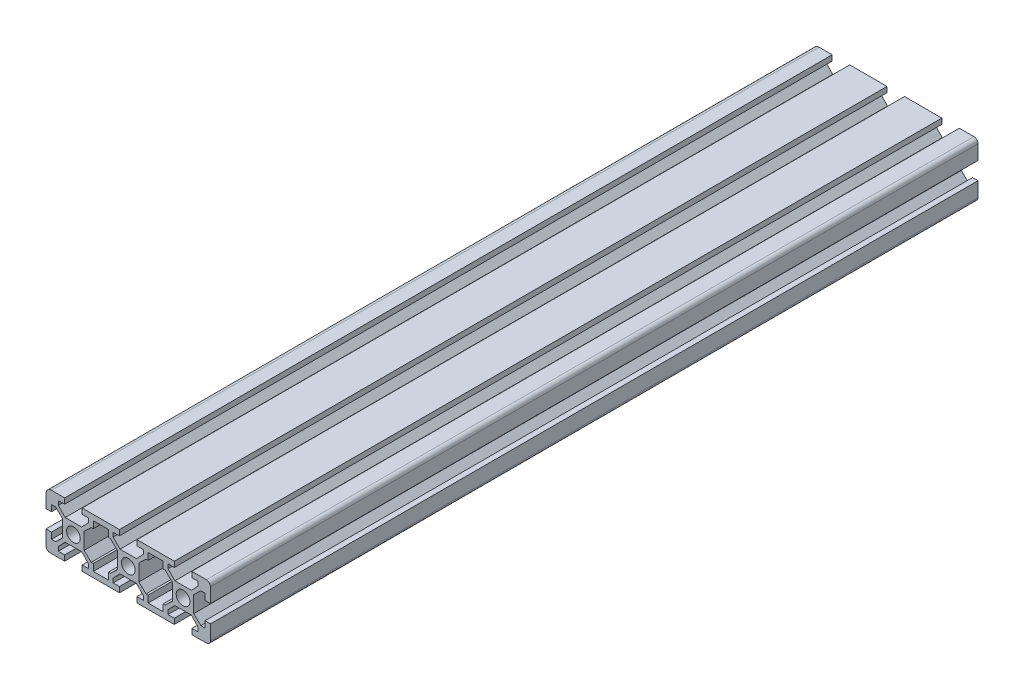
SolidWorks part; units mm, degrees
ref_plane "前视基准面" through (0, 0, 0) normal (0, 0, 1) x (1, 0, 0)
ref_plane "上视基准面" through (0, 0, 0) normal (0, 1, 0) x (1, 0, 0)
ref_plane "右视基准面" through (0, 0, 0) normal (1, 0, 0) x (0, 0, -1)
sketch "草图1" plane through (0, 0, 0) normal (0, 0, 1) x (1, 0, 0)
  line L1 (-28, 10) -> (28.5, 10)
  line L2 (-30, 8) -> (-30, -8.5)
  line L3 (-28.5, -10) -> (28.5, -10)
  line L4 (30, 8.5) -> (30, -8.5)
  line L5 (-30, 10) -> (30, -10) construction
  line L6 (-30, -10) -> (30, 10) construction
  line L7 (-30, -3.2) -> (-28, -3.2)
  line L13 (-16.8, 8) -> (-16.8, 10)
  line L14 (-14.5, 8) -> (-16.8, 8)
  line L15 (-14.5, 6.5) -> (-14.5, 8)
  line L16 (-17, 3.9) -> (-14.5, 6.5)
  line L17 (-23, 3.9) -> (-17, 3.9)
  line L18 (-25.5, 6.5) -> (-23, 3.9)
  line L25 (-28, -3.2) -> (-28, -5.5)
  line L26 (-28, -5.5) -> (-26.5, -5.5)
  line L27 (-26.5, -5.5) -> (-23.9, -3)
  line L28 (-23.9, -3) -> (-23.9, 3)
  line L29 (-23.9, 3) -> (-26.5, 5.5)
  line L30 (-26.5, 5.5) -> (-28, 5.5)
  line L31 (-28, 5.5) -> (-28, 3.2)
  line L32 (-28, 3.2) -> (-30, 3.2)
  line L33 (-25.5, 8) -> (-25.5, 6.5)
  line L34 (-23.2, 8) -> (-25.5, 8)
  line L35 (-23.2, 10) -> (-23.2, 8)
  line L36 (-12, -3.2) -> (-8, -3.2)
  line L37 (-12, -5.5) -> (-12, -3.2)
  line L38 (-13.5, -5.5) -> (-12, -5.5)
  line L39 (-16.1, -3) -> (-13.5, -5.5)
  line L40 (-16.1, 3) -> (-16.1, -3)
  line L41 (-13.5, 5.5) -> (-16.1, 3)
  line L42 (-12, 5.5) -> (-13.5, 5.5)
  line L43 (-12, 3.2) -> (-12, 5.5)
  line L44 (-8, 3.2) -> (-12, 3.2)
  line L45 (-23.2, -8) -> (-23.2, -10)
  line L46 (-25.5, -8) -> (-23.2, -8)
  line L47 (-25.5, -6.5) -> (-25.5, -8)
  line L48 (-23, -3.9) -> (-25.5, -6.5)
  line L49 (-17, -3.9) -> (-23, -3.9)
  line L50 (-14.5, -6.5) -> (-17, -3.9)
  line L51 (-14.5, -8) -> (-14.5, -6.5)
  line L52 (-16.8, -8) -> (-14.5, -8)
  line L53 (-16.8, -10) -> (-16.8, -8)
  line L54 (-10, 3.2) -> (-10, -3.2) construction
  line L55 (-10, -3.2) -> (-10, 3.2) construction
  line L56 (3, 3.9) -> (-3, 3.9)
  line L57 (5.5, 6.5) -> (3, 3.9)
  line L58 (5.5, 8) -> (5.5, 6.5)
  line L59 (3.2, 8) -> (5.5, 8)
  line L60 (3.2, 10) -> (3.2, 8)
  line L61 (-3.2, 8) -> (-3.2, 10)
  line L62 (-5.5, 8) -> (-3.2, 8)
  line L63 (-5.5, 6.5) -> (-5.5, 8)
  line L64 (-3, 3.9) -> (-5.5, 6.5)
  line L65 (-6.5, 5.5) -> (-3.9, 3)
  line L66 (-8, 5.5) -> (-6.5, 5.5)
  line L67 (-8, 3.2) -> (-8, 5.5)
  line L68 (-8, -5.5) -> (-8, -3.2)
  line L69 (-6.5, -5.5) -> (-8, -5.5)
  line L70 (-3.9, -3) -> (-6.5, -5.5)
  line L71 (-3.9, 3) -> (-3.9, -3)
  line L72 (-3, -3.9) -> (3, -3.9)
  line L73 (-5.5, -6.5) -> (-3, -3.9)
  line L74 (-5.5, -8) -> (-5.5, -6.5)
  line L75 (-3.2, -8) -> (-5.5, -8)
  line L76 (-3.2, -10) -> (-3.2, -8)
  line L77 (3.2, -8) -> (3.2, -10)
  line L78 (5.5, -8) -> (3.2, -8)
  line L79 (5.5, -6.5) -> (5.5, -8)
  line L80 (3, -3.9) -> (5.5, -6.5)
  line L81 (3.9, -3) -> (3.9, 3)
  line L82 (6.5, -5.5) -> (3.9, -3)
  line L83 (8, -5.5) -> (6.5, -5.5)
  line L84 (8, -3.2) -> (8, -5.5)
  line L85 (12, -3.2) -> (8, -3.2)
  line L86 (8, 3.2) -> (12, 3.2)
  line L87 (8, 5.5) -> (8, 3.2)
  line L88 (6.5, 5.5) -> (8, 5.5)
  line L89 (3.9, 3) -> (6.5, 5.5)
  line L90 (10, 3.2) -> (10, -3.133) construction
  line L91 (23.2, 8) -> (23.2, 10)
  line L92 (25.5, 8) -> (23.2, 8)
  line L93 (25.5, 6.5) -> (25.5, 8)
  line L94 (23, 3.9) -> (25.5, 6.5)
  line L95 (17, 3.9) -> (23, 3.9)
  line L96 (16.8, 10) -> (16.8, 8)
  line L97 (16.8, 8) -> (14.5, 8)
  line L98 (14.5, 8) -> (14.5, 6.5)
  line L99 (14.5, 6.5) -> (17, 3.9)
  line L100 (16.1, 3) -> (13.5, 5.5)
  line L101 (13.5, 5.5) -> (12, 5.5)
  line L102 (12, 5.5) -> (12, 3.2)
  line L103 (12, -3.2) -> (12, -5.5)
  line L104 (12, -5.5) -> (13.5, -5.5)
  line L105 (16.1, -3) -> (16.1, 3)
  line L106 (13.5, -5.5) -> (16.1, -3)
  line L107 (17, -3.9) -> (14.5, -6.5)
  line L108 (14.5, -6.5) -> (14.5, -8)
  line L109 (14.5, -8) -> (16.8, -8)
  line L110 (16.8, -8) -> (16.8, -10)
  line L111 (23.2, -10) -> (23.2, -8)
  line L112 (23.2, -8) -> (25.5, -8)
  line L113 (25.5, -8) -> (25.5, -6.5)
  line L114 (25.5, -6.5) -> (23, -3.9)
  line L115 (23, -3.9) -> (17, -3.9)
  line L116 (28, 3.2) -> (30, 3.2)
  line L117 (30, -3.2) -> (28, -3.2)
  line L118 (28, -5.5) -> (28, -3.2)
  line L119 (26.5, -5.5) -> (28, -5.5)
  line L120 (23.9, -3) -> (26.5, -5.5)
  line L121 (23.9, 3) -> (23.9, -3)
  line L122 (26.5, 5.5) -> (23.9, 3)
  line L123 (28, 5.5) -> (26.5, 5.5)
  line L124 (28, 3.2) -> (28, 5.5)
  line L125 (-12.75, 5.5) -> (-12.75, 8)
  line L126 (-7.25, 5.5) -> (-7.25, 8)
  line L127 (-7.25, 8) -> (-12.75, 8)
  line L128 (-12.75, -5.5) -> (-12.75, -8)
  line L129 (-7.25, -5.5) -> (-7.25, -8)
  line L130 (-7.25, -8) -> (-12.75, -8)
  line L131 (7.25, 5.5) -> (7.25, 8)
  line L132 (12.75, 5.5) -> (12.75, 8)
  line L133 (12.75, 8) -> (7.25, 8)
  line L134 (7.25, -5.5) -> (7.25, -8)
  line L135 (12.75, -5.5) -> (12.75, -8)
  line L136 (12.75, -8) -> (7.25, -8)
  circle A0 centre (0, 0) radius 2.5
  circle A1 centre (-20, 0) radius 2.5
  circle A2 centre (20, 0) radius 2.5
  arc A3 (-30, 8) -> (-28, 10) centre (-28, 8) cw
  arc A4 (-30, -8.5) -> (-28.5, -10) centre (-28.5, -8.5) ccw
  arc A5 (28.5, -10) -> (30, -8.5) centre (28.5, -8.5) ccw
  arc A6 (30, 8.5) -> (28.5, 10) centre (28.5, 8.5) ccw
  point P0 (0, 0)
  point P63 (-20, 0)
  point P115 (10, -3.2)
  dimension "D1" = 20
  dimension "D7" = 5
  dimension "D8" = 5
  dimension "D9" = 5
  dimension "D5" = 2
  dimension "D6" = 1.5
  dimension "D12" = 1.5
  dimension "D2" = 20
  dimension "D3" = 60
  dimension "D4" = 20
  dimension "D10" = 6.1
  dimension "D11" = 2.3
  dimension "D14" = 6.4
  dimension "D15" = 13.2
  dimension "D16" = 11
  dimension "D17" = 10
  dimension "D18" = 6
  dimension "D19" = 1.5
  dimension "D20" = 2
  dimension "D21" = 2
  dimension "D22" = 1.5
  dimension "D23" = 7
extrude "凸台-拉伸2" add sketch "草图1" along normal blind 280 contours L4 A6 L1 L91 L92 L93 L94 L95 L99 L98 L97 L96 L60 L59 L58 L57 L56 L64 L63 L62 L61 L13 L14 L15 L16 L17 L18 L33 L34 L35 A3 L2 L32 L31 L30 L29 L28 L27 L26 L25 L7 A4 L3 L45 L46 L47 L48 region at (-25.6, 9.3675, 0)
